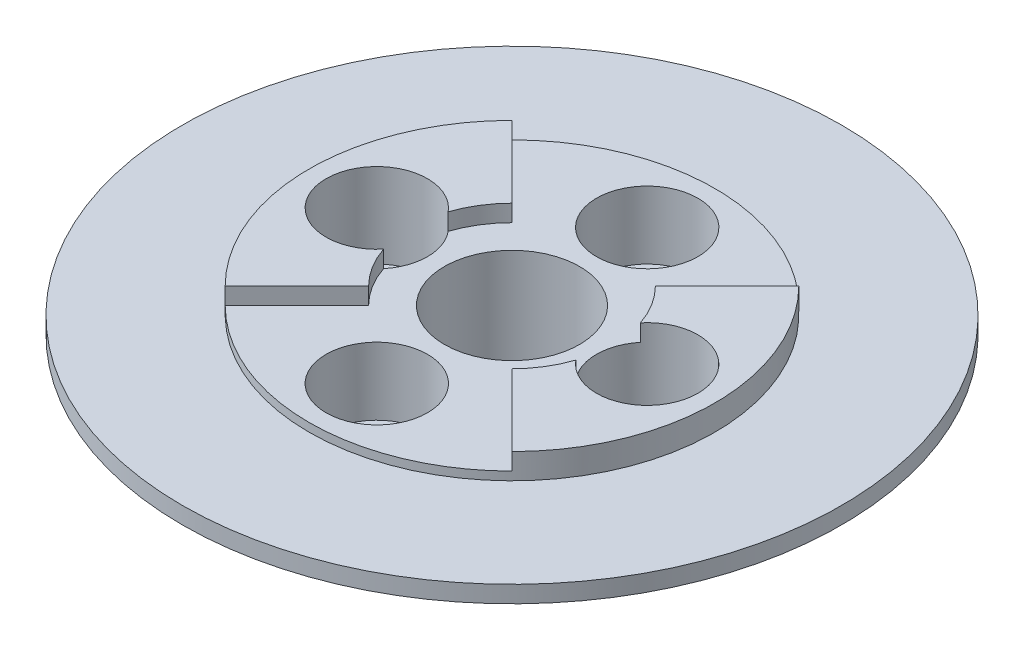
SolidWorks part; units mm, degrees
material "ABS"
ref_plane "Front" through (0, 0, 0) normal (0, 0, 1) x (1, 0, 0)
ref_plane "Top" through (0, 0, 0) normal (0, 1, 0) x (1, 0, 0)
ref_plane "Right" through (0, 0, 0) normal (1, 0, 0) x (0, 0, -1)
sketch "Szkic1" plane through (0, 0, 0) normal (0, 0, 1) x (1, 0, 0)
  line L88 (12, 0) -> (12.5, 0.5)
  line L89 (15, 4) -> (15, 4.5)
  line L90 (12.5, 4) -> (15, 4)
  line L91 (15, 4.5) -> (19.5, 4.5)
  line L93 (12, 5.5) -> (19.5, 5.5)
  line L94 (19.5, 4.5) -> (19.5, 5.5)
  line L95 (12.5, 0.5) -> (12.5, 4)
  line L96 (4, 6) -> (4, 0)
  line L97 (4, 0) -> (12, 0)
  line L98 (0, 6) -> (0, 0) construction
  line L112 (6, 6) -> (6, 7)
  line L113 (12, 7) -> (12, 5.5)
  line L114 (6, 7) -> (12, 7)
  line L192 (4, 6) -> (6, 6)
revolve "Obrót1" add sketch "Szkic1" angle 360 about L98
sketch "Szkic3" plane through (0, 7, 0) normal (0, 1, 0) x (1, 0, 0)
  circle A0 centre (0, -8) radius 1.5
  dimension "D1" = 8
  dimension "D2" = 3
extrude "Wytnij-wyciągnięcie1" cut sketch "Szkic3" against normal through all
sketch "Szkic4" plane through (0, 7, 0) normal (0, 1, 0) x (1, 0, 0)
  circle A0 centre (0, -8) radius 3
  dimension "D1" = 6
extrude "Wytnij-wyciągnięcie2" cut sketch "Szkic4" against normal blind 5
pattern_circular "Szyk kołowy1" count 4 over 360 about axis through (0, 6, 0) along (0, 1, 0) of "Wytnij-wyciągnięcie2", "Wytnij-wyciągnięcie1" reverse direction yes
sketch "Szkic5" plane through (0, 7, 0) normal (0, 1, 0) x (1, 0, 0)
  line L0 (0, 0) -> (0, 14.4554) construction
  line L1 (-8.4853, -8.4853) -> (-4.2426, -4.2426)
  line L2 (8.4853, -8.4853) -> (4.2426, -4.2426)
  line L3 (4.2426, 4.2426) -> (8.4853, 8.4853)
  line L4 (-4.2426, 4.2426) -> (-8.4853, 8.4853)
  arc A0 (-4.2426, -4.2426) -> (4.2426, -4.2426) centre (0, 0) ccw
  arc A1 (-8.4853, -8.4853) -> (8.4853, -8.4853) centre (0, 0) ccw
  arc A2 (4.2426, 4.2426) -> (-4.2426, 4.2426) centre (0, 0) ccw
  arc A3 (8.4853, 8.4853) -> (-8.4853, 8.4853) centre (0, 0) ccw
  dimension "D1" = 45
extrude "Wytnij-wyciągnięcie3" cut sketch "Szkic5" against normal blind 1
